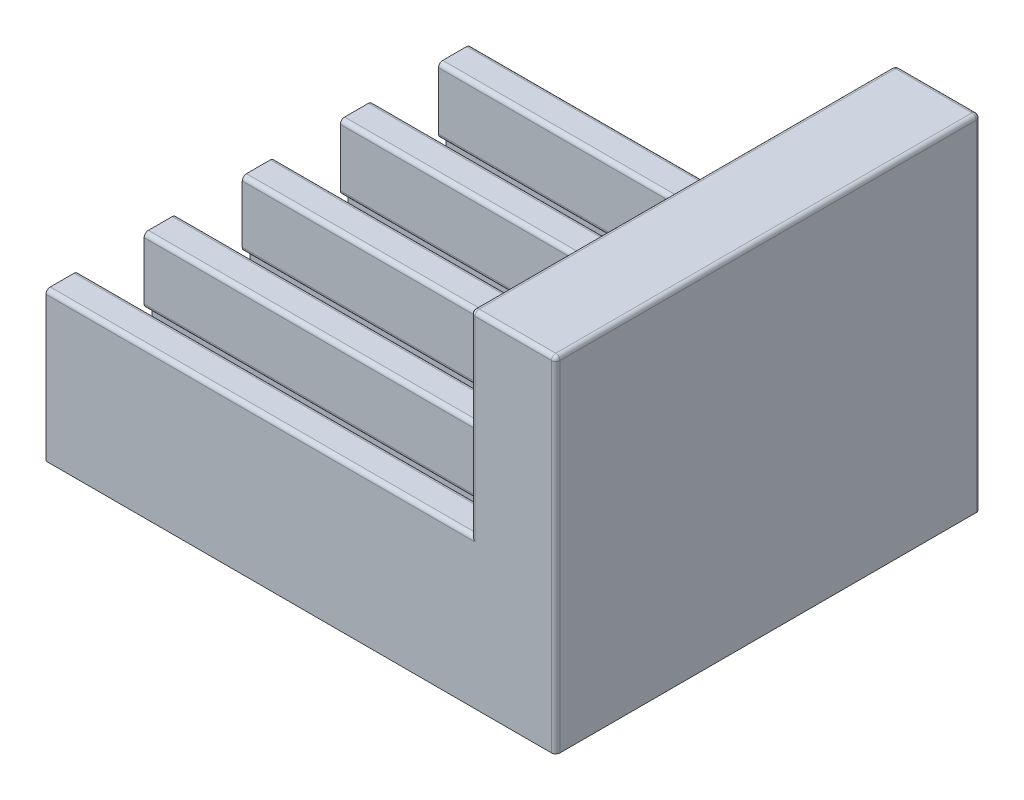
SolidWorks part; units mm, degrees
ref_plane "Front Plane" through (0, 0, 0) normal (0, 0, 1) x (1, 0, 0)
ref_plane "Top Plane" through (0, 0, 0) normal (0, 1, 0) x (1, 0, 0)
ref_plane "Right Plane" through (0, 0, 0) normal (1, 0, 0) x (0, 0, -1)
sketch "Sketch1" plane through (0, 0, 0) normal (0, 1, 0) x (1, 0, 0)
  line L1 (-63.5354, 42.4181) -> (56.4646, 42.4181)
  line L2 (-63.5354, 42.4181) -> (-63.5354, -57.5819)
  line L3 (-63.5354, -57.5819) -> (56.4646, -57.5819)
  line L4 (56.4646, 42.4181) -> (56.4646, -57.5819)
  dimension "D1" = 100
  dimension "D2" = 120
extrude "Boss-Extrude1" add sketch "Sketch1" along normal blind 81
sketch "Sketch2" plane through (0, 81, 0) normal (0, 1, 0) x (1, 0, 0)
  line L0 (-63.5354, -57.5819) -> (56.4646, -57.5819) construction
  line L1 (-63.5354, 42.4181) -> (36.4646, 42.4181)
  line L2 (-63.5354, 42.4181) -> (-63.5354, -57.5819)
  line L3 (-63.5354, -57.5819) -> (36.4646, -57.5819)
  line L4 (36.4646, 42.4181) -> (36.4646, -57.5819)
  dimension "D1" = 100
extrude "Cut-Extrude1" cut sketch "Sketch2" against normal blind 46
sketch "Sketch6" plane through (-63.5354, 0, 0) normal (-1, 0, 0) x (0, 0, 1)
  line L0 (57.5819, 35) -> (-42.4181, 35) construction
  line L1 (-34.8181, 35) -> (-19.3181, 35)
  line L2 (-34.8181, 35) -> (-34.8181, 19.5)
  line L3 (-34.8181, 19.5) -> (-19.3181, 19.5)
  line L4 (-19.3181, 35) -> (-19.3181, 19.5)
  line L5 (-19.3181, 27.25) -> (-11.7181, 27.25) construction
  line L6 (-11.7181, 35) -> (3.7819, 35)
  line L7 (-11.7181, 35) -> (-11.7181, 19.5)
  line L8 (-11.7181, 19.5) -> (3.7819, 19.5)
  line L9 (3.7819, 35) -> (3.7819, 19.5)
  line L10 (11.3819, 35) -> (26.8819, 35)
  line L11 (11.3819, 35) -> (11.3819, 19.5)
  line L12 (11.3819, 19.5) -> (26.8819, 19.5)
  line L13 (26.8819, 35) -> (26.8819, 19.5)
  line L14 (34.4819, 35) -> (49.9819, 35)
  line L15 (34.4819, 35) -> (34.4819, 19.5)
  line L16 (34.4819, 19.5) -> (49.9819, 19.5)
  line L17 (49.9819, 35) -> (49.9819, 19.5)
  line L18 (-15.5181, 27.25) -> (-15.5181, 0) construction
  line L19 (-42.4181, 0) -> (57.5819, 0) construction
  line L20 (7.5819, 35) -> (7.5819, 0) construction
  line L21 (-42.4181, 35) -> (57.5819, 35) construction
  circle A0 centre (-27.0681, 27.25) radius 5.95
  circle A1 centre (-3.9681, 27.25) radius 5.95
  circle A2 centre (42.2319, 27.25) radius 5.95
  circle A3 centre (19.1319, 27.25) radius 5.95
  dimension "D13" = 7.75
  dimension "D1" = 15.5
  dimension "D2" = 15.5
  dimension "D3" = 15.5
  dimension "D4" = 15.5
  dimension "D5" = 15.5
  dimension "D6" = 15.5
  dimension "D7" = 15.5
  dimension "D8" = 15.5
  dimension "D9" = 7.6
  dimension "D10" = 7.6
  dimension "D11" = 7.6
  dimension "D12" = 7.6
  dimension "D14" = 7.75
extrude "Cut-Extrude4" cut sketch "Sketch6" against normal blind 100 contours L11 L10 L13 L12 | L15 L14 L17 L16 | L7 L6 L9 L8 | L2 L1 L4 L3
sketch "Sketch8" plane through (-63.5354, 0, 0) normal (-1, 0, 0) x (0, 0, 1)
  line L1 (-36.6181, 19.5) -> (-17.5181, 19.5)
  line L2 (-36.6181, 19.5) -> (-36.6181, 9.5)
  line L3 (-36.6181, 9.5) -> (-17.5181, 9.5)
  line L4 (-17.5181, 19.5) -> (-17.5181, 9.5)
  line L6 (-15.5181, 35) -> (-15.5181, 0) construction
  line L7 (-19.3181, 35) -> (-11.7181, 35) construction
  line L8 (-42.4181, 0) -> (57.5819, 0) construction
  line L9 (5.5819, 9.5) -> (-13.5181, 9.5)
  line L10 (-13.5181, 19.5) -> (-13.5181, 9.5)
  line L11 (5.5819, 19.5) -> (-13.5181, 19.5)
  line L12 (5.5819, 19.5) -> (5.5819, 9.5)
  line L13 (7.5819, 35) -> (7.5819, 0) construction
  line L14 (11.3819, 35) -> (3.7819, 35) construction
  line L15 (51.7819, 9.5) -> (32.6819, 9.5)
  line L16 (32.6819, 19.5) -> (32.6819, 9.5)
  line L17 (51.7819, 19.5) -> (32.6819, 19.5)
  line L18 (51.7819, 19.5) -> (51.7819, 9.5)
  line L19 (9.5819, 19.5) -> (9.5819, 9.5)
  line L20 (9.5819, 19.5) -> (28.6819, 19.5)
  line L21 (28.6819, 19.5) -> (28.6819, 9.5)
  line L22 (9.5819, 9.5) -> (28.6819, 9.5)
  dimension "D1" = 1.8
  dimension "D2" = 10
  dimension "D3" = 19.1
extrude "Cut-Extrude5" cut sketch "Sketch8" against normal blind 100
extrude "Cut-Extrude6" cut sketch "Sketch6<3>" against normal blind 111 contours A0 | A1 | A3 | A2 region at (-63.5354, 27.25, -27.0681) region at (-63.5354, 27.25, -3.9681) region at (-63.5354, 27.25, 42.2319) region at (-63.5354, 27.25, 19.1319)
sketch "Sketch6<3>" plane through (-63.5354, 0, 0) normal (-1, 0, 0) x (0, 0, 1) same geometry as "Sketch6"
fillet "Fillet1" radius 1 10 edges at (-13.5354, 35, -42.4181) (-13.5354, 35, 57.5819) (36.4646, 58, -42.4181) (36.4646, 58, 57.5819) (46.4646, 81, 57.5819) (36.4646, 81, 7.5819) (46.4646, 81, -42.4181) (56.4646, 81, 7.5819) (56.4646, 40.5, 57.5819) (56.4646, 40.5, -42.4181)
chamfer "Chamfer1" distance 1 angle 45 4 edges at (36.4646, 27.25, 36.2819) (36.4646, 27.25, 13.1819) (36.4646, 27.25, -9.9181) (36.4646, 27.25, -33.0181)
fillet "Fillet2" radius 1 4 edges at (47.4646, 27.25, 48.1819) (47.4646, 27.25, 25.0819) (47.4646, 27.25, 1.9819) (47.4646, 27.25, -21.1181)
fillet "Fillet3" radius 1 16 edges at (-13.5354, 19.5, -19.3181) (-13.5354, 19.5, 3.7819) (-13.5354, 19.5, 26.8819) (-13.5354, 19.5, -34.8181) (-13.5354, 19.5, -11.7181) (-13.5354, 19.5, 11.3819) (-13.5354, 19.5, 34.4819) (-13.5354, 19.5, 49.9819) (-13.5354, 35, -34.8181) (-13.5354, 35, -19.3181) (-13.5354, 35, -11.7181) (-13.5354, 35, 3.7819) (-13.5354, 35, 26.8819) (-13.5354, 35, 11.3819) (-13.5354, 35, 34.4819) (-13.5354, 35, 49.9819)
